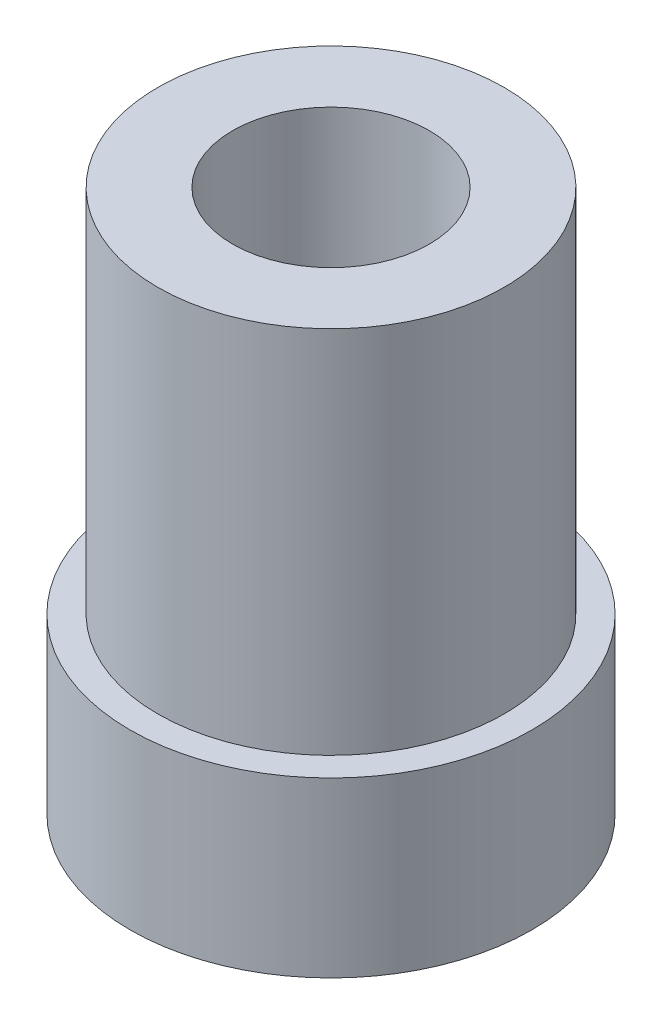
SolidWorks part; units mm, degrees
ref_plane "Front Plane" through (0, 0, 0) normal (0, 0, 1) x (1, 0, 0)
ref_plane "Top Plane" through (0, 0, 0) normal (0, 1, 0) x (1, 0, 0)
ref_plane "Right Plane" through (0, 0, 0) normal (1, 0, 0) x (0, 0, -1)
sketch "Sketch1" plane through (0, 0, 0) normal (0, 1, 0) x (1, 0, 0)
  circle A0 centre (0, 0) radius 5.5245
  dimension "D1" = 11.049
extrude "Boss-Extrude1" add sketch "Sketch1" along normal blind 4.7625
sketch "Sketch2" plane through (0, 4.7625, 0) normal (0, 1, 0) x (1, 0, 0)
  circle A0 centre (0, 0) radius 4.7625
  dimension "D1" = 9.525
extrude "Boss-Extrude2" add sketch "Sketch2" along normal blind 10.16
sketch "Sketch3" plane through (0, 14.9225, 0) normal (0, 1, 0) x (1, 0, 0)
  circle A0 centre (0, 0) radius 2.7051
  dimension "D1" = 5.4102
extrude "Cut-Extrude1" cut sketch "Sketch3" against normal through all
